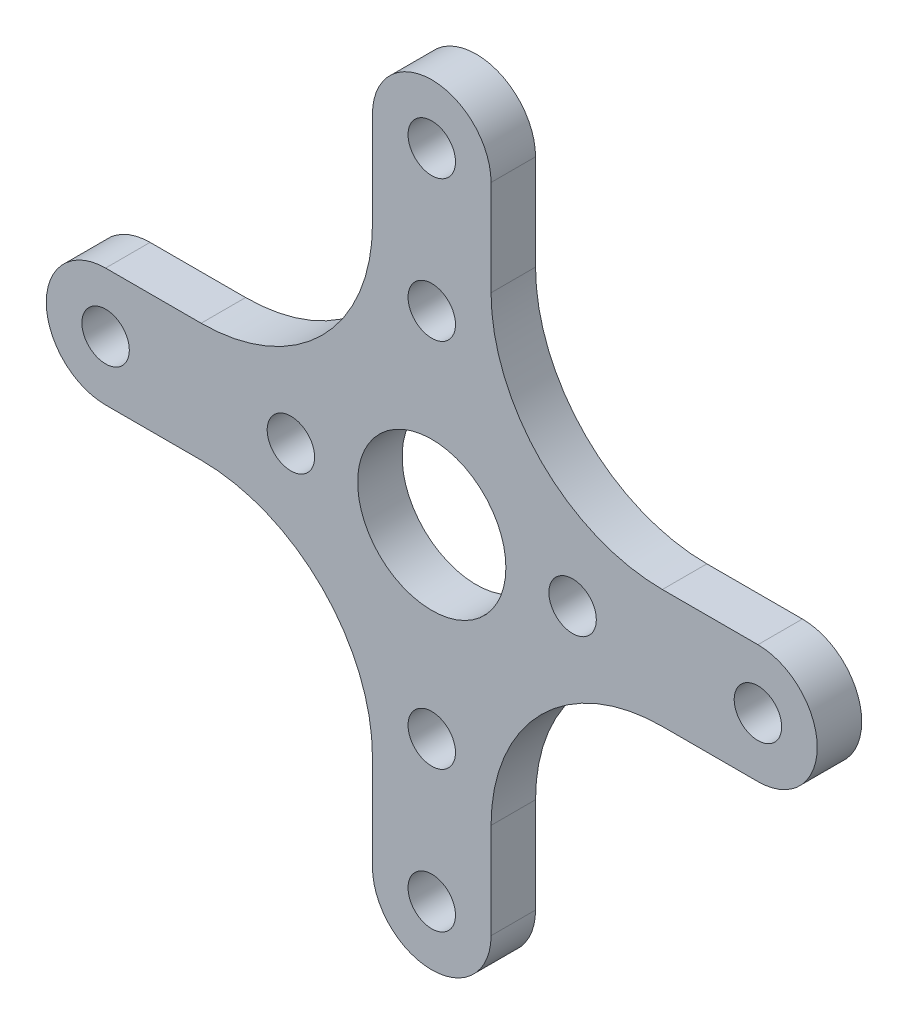
SolidWorks part; units mm, degrees
ref_plane "Front Plane" through (0, 0, 0) normal (0, 0, 1) x (1, 0, 0)
ref_plane "Top Plane" through (0, 0, 0) normal (0, 1, 0) x (1, 0, 0)
ref_plane "Right Plane" through (0, 0, 0) normal (1, 0, 0) x (0, 0, -1)
sketch "Эскиз1" plane through (0, 0, 0) normal (0, 0, 1) x (1, 0, 0)
  line L0 (0, 96.3109) -> (0, -96.3109) construction
  line L1 (-81.2237, 0) -> (103.8753, 0) construction
  line L2 (-22, 4) -> (-15.5563, 4)
  line L3 (-4, 15.5563) -> (-4, 22)
  line L4 (22, 4) -> (15.5563, 4)
  line L5 (4, 15.5563) -> (4, 22)
  line L6 (22, -4) -> (15.5563, -4)
  line L7 (4, -15.5563) -> (4, -22)
  line L8 (-4, -15.5563) -> (-4, -22)
  line L9 (-22, -4) -> (-15.5563, -4)
  circle A0 centre (0, 0) radius 22 construction
  circle A1 centre (0, 22) radius 1.6
  circle A2 centre (22, 0) radius 1.6
  circle A3 centre (0, -22) radius 1.6
  circle A4 centre (-22, 0) radius 1.6
  circle A5 centre (0, 0) radius 5
  circle A6 centre (-9.5, 0) radius 1.6
  circle A7 centre (9.5, 0) radius 1.6
  circle A8 centre (0, 12.5) radius 1.6
  circle A9 centre (0, -12.5) radius 1.6
  arc A10 (-15.5563, 4) -> (-4, 15.5563) centre (-15.5563, 15.5563) ccw
  arc A11 (-4, 22) -> (4, 22) centre (0, 22) cw
  arc A12 (-22, 4) -> (-22, -4) centre (-22, 0) ccw
  arc A13 (22, 4) -> (22, -4) centre (22, 0) cw
  arc A14 (15.5563, 4) -> (4, 15.5563) centre (15.5563, 15.5563) cw
  arc A15 (15.5563, -4) -> (4, -15.5563) centre (15.5563, -15.5563) ccw
  arc A16 (-4, -22) -> (4, -22) centre (0, -22) ccw
  arc A17 (-15.5563, -4) -> (-4, -15.5563) centre (-15.5563, -15.5563) cw
  dimension "D1" = 44
  dimension "D2" = 3.2
  dimension "D4" = 3.2
  dimension "D6" = 3.2
  dimension "D9" = 10
  dimension "D3" = 19
  dimension "D5" = 9.5
  dimension "D7" = 25
  dimension "D8" = 12.5
extrude "Бобышка-Вытянуть1" add sketch "Эскиз1" along normal mid plane 3
ref_axis "Ось1" through (0, 0, 24.7187) along (0, 0, -1)
equation "\"D5@Эскиз1\"=\"D3@Эскиз1\"/2"
equation "\"D8@Эскиз1\"=\"D7@Эскиз1\"/2"
